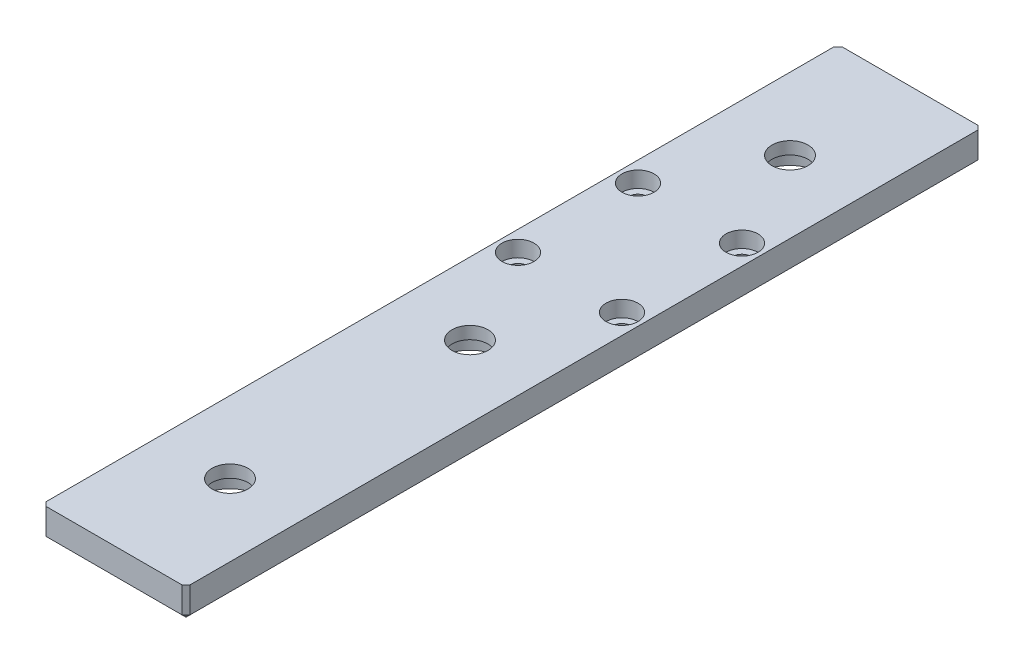
SolidWorks part; units mm, degrees
ref_plane "Front Plane" through (0, 0, 0) normal (0, 0, 1) x (1, 0, 0)
ref_plane "Top Plane" through (0, 0, 0) normal (0, 1, 0) x (1, 0, 0)
ref_plane "Right Plane" through (0, 0, 0) normal (1, 0, 0) x (0, 0, -1)
sketch "Sketch1" plane through (0, 0, 0) normal (0, 1, 0) x (1, 0, 0)
  line L1 (-18, 99.5) -> (18, 99.5)
  line L2 (-18, 99.5) -> (-18, -99.5)
  line L3 (-18, -99.5) -> (18, -99.5)
  line L4 (18, 99.5) -> (18, -99.5)
  line L5 (-18, 99.5) -> (18, -99.5) construction
  line L6 (-18, -99.5) -> (18, 99.5) construction
  point P0 (0, 0)
  dimension "D1" = 199
  dimension "D2" = 36
extrude "Boss-Extrude1" add sketch "Sketch1" along normal blind 7.5
hole_wizard "CBORE for M4 SHCS1" positions "Sketch2" profile "Sketch3" counterbore size "M4" standard "ANSI Metric" end condition through all
sketch "Sketch2" plane through (0, 7.5, 0) normal (0, 1, 0) x (1, 0, 0)
  line L0 (-13, 44.5) -> (13, 14.5) construction
  line L2 (18, 99.5) -> (-18, 99.5) construction
  point P0 (-13, 44.5)
  point P2 (13, 44.5)
  point P4 (13, 14.5)
  point P6 (-13, 14.5)
  point P22 (0, 29.5)
  dimension "D1" = 30
  dimension "D2" = 26
  dimension "D3" = 70
sketch "Sketch3" plane through (-13, 7.5, -44.5) normal (1, 0, 0) x (0, 0, 1)
  line L0 (0, 0) -> (0, 7.5)
  line L1 (0, 7.5) -> (2.25, 7.5)
  line L3 (2.25, 7.5) -> (2.25, 4)
  line L4 (2.25, 4) -> (4, 4)
  line L5 (4, 4) -> (4, 0)
  line L7 (4, 0) -> (0, 0)
  line L11 (0, -6.35) -> (0, 107.95) construction
  dimension "Thru Hole Dia." = 4.5
  dimension "Thru Hole Depth" = 7.5
  dimension "C'Bore Dia." = 8
  dimension "C'Bore Depth" = 4
chamfer "Chamfer1" distance 1 angle 45 8 edges at (-18, 3.75, -99.5) (18, 3.75, -99.5) (-18, 3.75, 99.5) (18, 3.75, 99.5) (0, 0, -99.5) (-18, 0, 0) (0, 0, 99.5) (18, 0, 0)
hole_wizard "CBORE for M8 SBHCS1" positions "Sketch4" profile "Sketch5" counterbore size "M8" standard "ANSI Metric" end condition through all
sketch "Sketch4" plane through (0, 0, 0) normal (0, -1, 0) x (-1, 0, 0)
  line L0 (0, 69.5) -> (0, -10.5) construction
  line L2 (-17, 99.5) -> (17, 99.5) construction
  point P0 (0, 69.5)
  point P2 (0, -10.5)
  point P4 (0, -70.5)
  point P10 (0, 29.5)
  point P13 (0, 0)
  point P14 (7.0262, -10.5)
  point P16 (0, 0)
  dimension "D1" = 80
  dimension "D2" = 60
  dimension "D3" = 70
sketch "Sketch5" plane through (0, 0, -69.5) normal (1, 0, 0) x (0, 0, -1)
  line L0 (0, 0) -> (0, 7.5)
  line L1 (0, 7.5) -> (4.5, 7.5)
  line L3 (4.5, 7.5) -> (4.5, 4.4)
  line L4 (4.5, 4.4) -> (7.5, 4.4)
  line L5 (7.5, 4.4) -> (7.5, 0)
  line L7 (7.5, 0) -> (0, 0)
  line L11 (0, -6.35) -> (0, 107.95) construction
  dimension "Thru Hole Dia." = 9
  dimension "Thru Hole Depth" = 7.5
  dimension "C'Bore Dia." = 15
  dimension "C'Bore Depth" = 4.4
